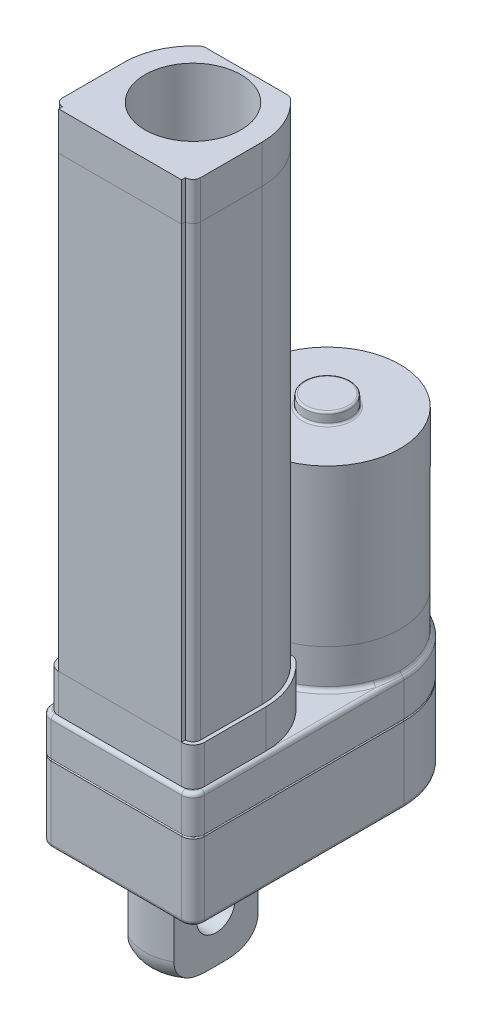
SolidWorks part; units mm, degrees
note: The reader was unsure of these and kept them because the rebuilt part matched: shared geometry of "Sketch1<4>", "Sketch1<5>".
ref_plane "Front Plane" through (0, 0, 0) normal (0, 0, 1) x (1, 0, 0)
ref_plane "Top Plane" through (0, 0, 0) normal (0, 1, 0) x (1, 0, 0)
ref_plane "Right Plane" through (0, 0, 0) normal (1, 0, 0) x (0, 0, -1)
sketch "Sketch1" plane through (0, 0, 0) normal (0, 1, 0) x (1, 0, 0)
  line L0 (0, 0) -> (0, 35) construction
  line L1 (-20, -16.958) -> (-20, 35)
  line L2 (20, -16.958) -> (20, 35)
  line L3 (-17, -19.958) -> (17, -19.958)
  line L4 (-10.583, 15) -> (10.583, 15)
  line L5 (-19, 0) -> (-19, -16)
  line L6 (-16, -19) -> (16, -19)
  line L7 (19, 0) -> (19, -16)
  arc A1 (20, 35) -> (-20, 35) centre (0, 35) ccw
  circle A2 centre (0, 35) radius 19
  arc A3 (19, 0) -> (12.5673, 14.25) centre (0, 0) ccw
  arc A4 (-12.5673, 14.25) -> (-19, 0) centre (0, 0) ccw
  arc A5 (12.5673, 14.25) -> (10.583, 15) centre (10.583, 12) ccw
  arc A6 (-12.5673, 14.25) -> (-10.583, 15) centre (-10.583, 12) cw
  arc A7 (-19, -16) -> (-16, -19) centre (-16, -16) ccw
  arc A8 (16, -19) -> (19, -16) centre (16, -16) ccw
  arc A9 (17, -19.958) -> (20, -16.958) centre (17, -16.958) ccw
  arc A10 (-17, -19.958) -> (-20, -16.958) centre (-17, -16.958) cw
  point P3 (0, 17.5)
  point P16 (0, 15)
  point P24 (-19, -19)
  point P27 (19, -19)
  dimension "D3" = 38
  dimension "D1" = 3
  dimension "D2" = 40
  dimension "D4" = 38
  dimension "D6" = 20
extrude "Boss-Extrude1" add sketch "Sketch1" against normal blind 30
fillet "Fillet1" radius 1 12 edges at (19.1213, 0, 19.0793) (0, 0, 19.958) (-19.1213, 0, 19.0793) (-20, 0, -9.021) (0, 0, -55) (19.1213, -30, 19.0793) (0, -30, 19.958) (-19.1213, -30, 19.0793) (-20, -30, -9.021) (0, -30, -55) (20, 0, -9.021) (20, -30, -9.021)
extrude "Boss-Extrude2" add sketch "Sketch1<4>" along normal blind 50.8
sketch "Sketch1<4>" plane through (0, 0, 0) normal (0, 1, 0) x (1, 0, 0) same geometry as "Sketch1"
extrude "Boss-Extrude3" add sketch "Sketch1<5>" along normal blind 10
sketch "Sketch1<5>" plane through (0, 0, 0) normal (0, 1, 0) x (1, 0, 0) same geometry as "Sketch1"
sketch "Sketch2" plane through (0, 10, 0) normal (0, 1, 0) x (1, 0, 0)
  line L0 (-18, 0) -> (-18, -16)
  line L2 (18, -16) -> (18, 0)
  line L3 (10.583, 14) -> (-10.583, 14)
  line L4 (10.583, 15) -> (-10.583, 15)
  line L5 (-19, 0) -> (-19, -16)
  line L6 (-16, -19) -> (16, -19)
  line L7 (19, -16) -> (19, 0)
  line L10 (-16, -19) -> (16, -19)
  line L12 (-16, -18) -> (-16, -19)
  line L13 (16, -18) -> (16, -19)
  line L15 (-16, -18) -> (16, -18) construction
  line L16 (-19, 0) -> (-19, -16) construction
  line L17 (10.583, 15) -> (-10.583, 15) construction
  line L18 (19, -16) -> (19, 0) construction
  arc A0 (-11.9059, 13.5) -> (-18, 0) centre (0, 0) ccw
  arc A1 (-18, -16) -> (-16, -18) centre (-16, -16) ccw
  arc A2 (16, -18) -> (18, -16) centre (16, -16) ccw
  arc A3 (18, 0) -> (11.9059, 13.5) centre (0, 0) ccw
  arc A4 (11.9059, 13.5) -> (10.583, 14) centre (10.583, 12) ccw
  arc A5 (-10.583, 14) -> (-11.9059, 13.5) centre (-10.583, 12) ccw
  arc A6 (-10.583, 15) -> (-12.5673, 14.25) centre (-10.583, 12) ccw
  arc A7 (-12.5673, 14.25) -> (-19, 0) centre (0, 0) ccw
  arc A8 (-19, -16) -> (-16, -19) centre (-16, -16) ccw
  arc A9 (16, -19) -> (19, -16) centre (16, -16) ccw
  arc A10 (19, 0) -> (12.5673, 14.25) centre (0, 0) ccw
  arc A11 (12.5673, 14.25) -> (10.583, 15) centre (10.583, 12) ccw
  arc A15 (16, -19) -> (19, -16) centre (16, -16) ccw construction
  arc A18 (-19, -16) -> (-16, -19) centre (-16, -16) ccw construction
  arc A19 (-12.5673, 14.25) -> (-19, 0) centre (0, 0) ccw construction
  arc A20 (-10.583, 15) -> (-12.5673, 14.25) centre (-10.583, 12) ccw construction
  arc A21 (12.5673, 14.25) -> (10.583, 15) centre (10.583, 12) ccw construction
  arc A22 (19, 0) -> (12.5673, 14.25) centre (0, 0) ccw construction
  dimension "D1" = 0
  dimension "D2" = 1
extrude "Boss-Extrude4" add sketch "Sketch2" along normal blind 127 separate body
sketch "Sketch3" plane through (0, 50.8, 0) normal (0, 1, 0) x (1, 0, 0)
  circle A0 centre (0, 35) radius 6
  dimension "D1" = 12
extrude "Boss-Extrude5" add sketch "Sketch3" along normal blind 3
sketch "Sketch4" plane through (0, 0, 0) normal (1, 0, 0) x (0, 0, -1)
  line L0 (16, 10) -> (55.3385, 10)
  line L1 (16, 50.8) -> (16, 0) construction
  line L2 (-25.9916, 127) -> (23.2347, 127)
  line L3 (-16, 137) -> (0, 137) construction
  line L4 (56.829, 96.7374) -> (14.8124, 96.7374)
  line L5 (14.8124, 95.4767) -> (56.829, 95.4767)
  point P13 (0, 0)
  dimension "D1" = 10
split line "Split Line1"
fillet "Fillet2" radius 1 2 edges at (0, 0, -54) (0, 0, -16)
fillet "Fillet3" radius 0.5 2 edges at (0, 53.8, -29) (0, 50.8, -29)
sketch "Sketch5" plane through (0, 137, 0) normal (0, 1, 0) x (1, 0, 0)
  circle A0 centre (0, 0) radius 12.5
  dimension "D1" = 25
extrude "Cut-Extrude4" cut sketch "Sketch5" against normal blind 500 contours A0
sketch "Sketch6" plane through (0, -30, 0) normal (0, -1, 0) x (1, 0, 0)
  line L0 (0, 12.5) -> (0, -15.5053) construction
  line L1 (-6, 10.9659) -> (-6, -10.9659)
  line L2 (6, 10.9659) -> (6, -10.9659)
  line L3 (6, 12.5) -> (6, -15.5053) construction
  line L4 (-6, 12.5) -> (-6, -15.5053) construction
  arc A0 (-6, -10.9659) -> (6, -10.9659) centre (0, 0) ccw
  arc A1 (6, 10.9659) -> (-6, 10.9659) centre (0, 0) ccw
  dimension "D1" = 25
  dimension "D2" = 6
  dimension "D3" = 6
extrude "Boss-Extrude7" add sketch "Sketch6" along normal blind 25
sketch "Sketch8" plane through (0, 0, 0) normal (1, 0, 0) x (0, 0, -1)
  line L0 (10.9659, -55) -> (-10.9659, -55) construction
  circle A0 centre (0, -42.5) radius 5
  dimension "D1" = 10
  dimension "D2" = 12.5
extrude "Cut-Extrude5" cut sketch "Sketch8" against normal through all both and the other way through all
ref_plane "Plane1" through (0, -10, 0) normal (0, -1, 0) x (-1, 0, 0)
sketch "Sketch9" plane through (0, -10, 0) normal (0, -1, 0) x (-1, 0, 0)
  line L0 (-20, -16.958) -> (-20, 35) construction
  line L1 (17, -19.958) -> (-17, -19.958) construction
  line L2 (20, -16.958) -> (20, 35) construction
  line L3 (-20, -16.958) -> (-20, 35)
  line L4 (17, -19.958) -> (-17, -19.958)
  line L5 (20, -16.958) -> (20, 35)
  arc A0 (-20, -16.958) -> (-17, -19.958) centre (-17, -16.958) ccw construction
  arc A1 (17, -19.958) -> (20, -16.958) centre (17, -16.958) ccw construction
  arc A2 (20, 35) -> (-20, 35) centre (0, 35) ccw construction
  arc A3 (-20, -16.958) -> (-17, -19.958) centre (-17, -16.958) ccw
  arc A4 (17, -19.958) -> (20, -16.958) centre (17, -16.958) ccw
  arc A5 (20, 35) -> (-20, 35) centre (0, 35) ccw
sweep "Cut-Sweep1" cut path "Sketch9" circular profile diameter 0.5 parameters "D3"=0.5
fillet "Fillet4" radius 6.35 2 edges at (0, -55, -12.5) (0, -55, 12.5)
